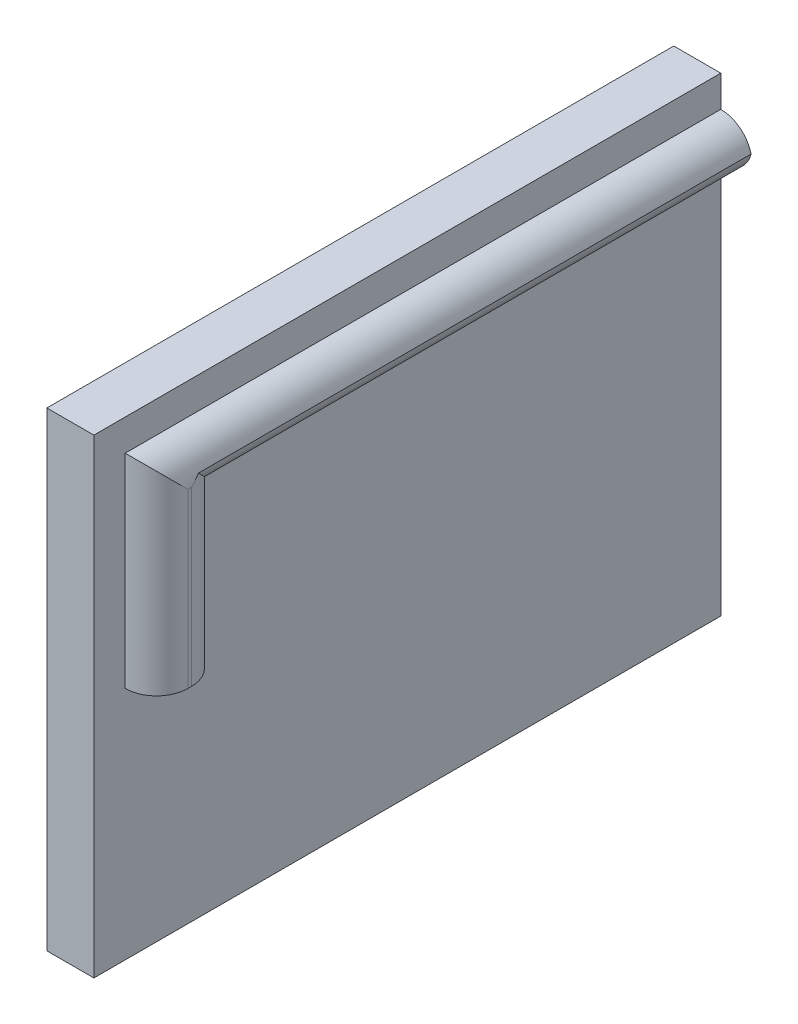
SolidWorks part; units mm, degrees
ref_plane "Front Plane" through (0, 0, 0) normal (0, 0, 1) x (1, 0, 0)
ref_plane "Top Plane" through (0, 0, 0) normal (0, 1, 0) x (1, 0, 0)
ref_plane "Right Plane" through (0, 0, 0) normal (1, 0, 0) x (0, 0, -1)
sketch "Sketch1" plane through (0, 0, 0) normal (1, 0, 0) x (0, 0, -1)
  line L1 (-20, 15) -> (20, 15)
  line L2 (-20, 15) -> (-20, -15)
  line L3 (-20, -15) -> (20, -15)
  line L4 (20, 15) -> (20, -15)
  line L5 (-20, 15) -> (20, -15) construction
  line L6 (-20, -15) -> (20, 15) construction
  point P0 (0, 0)
  dimension "D1" = 40
  dimension "D2" = 30
extrude "Boss-Extrude1" add sketch "Sketch1" along normal blind 3
sketch "Sketch2" plane through (3, 0, 0) normal (1, 0, 0) x (0, 0, -1)
  line L0 (20, -15) -> (20, 15) construction
  line L1 (20, 13) -> (-18, 13)
  line L2 (20, 13) -> (20, 10)
  line L3 (20, 10) -> (-13.7685, 10)
  line L4 (-18, 13) -> (-18, 10)
  line L5 (-20, 15) -> (-20, -15) construction
  line L6 (-20, -15) -> (20, -15) construction
  line L7 (-18, 13) -> (-13.7685, 13)
  line L8 (-18, 13) -> (-18, 0)
  line L9 (-18, 0) -> (-13.7685, 0)
  line L10 (-13.7685, 10) -> (-13.7685, 0)
  line M8 (20, -15) -> (20, 15)
  dimension "D1" = 2
  dimension "D2" = 3
  dimension "D3" = 2
  dimension "D4" = 15
extrude "Boss-Extrude2" add sketch "Sketch2" along normal blind 2 contours L10 L3 L1 L4 L8 L9 M8 region at (3, 11.5, -19.5984)
fillet "Fillet1" radius 2 4 edges at (5, 6.5, 18) (5, 5, 13.7685) (5, 10, -3.1157) (5, 13, -1)
